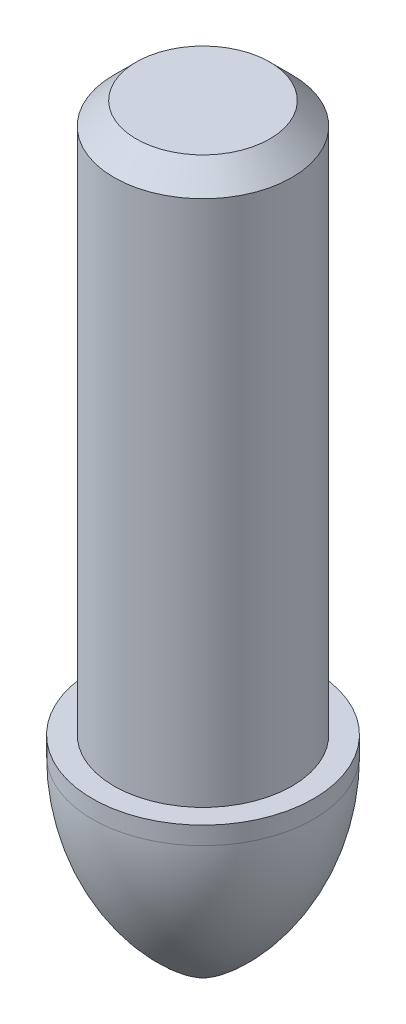
SolidWorks part; units mm, degrees
material "K110"
ref_plane "Front Plane" through (0, 0, 0) normal (0, 0, 1) x (1, 0, 0)
ref_plane "Top Plane" through (0, 0, 0) normal (0, 1, 0) x (1, 0, 0)
ref_plane "Right Plane" through (0, 0, 0) normal (1, 0, 0) x (0, 0, -1)
sketch "Sketch1" plane through (0, 0, 0) normal (0, 0, 1) x (1, 0, 0)
  line L0 (0, 0) -> (0, -39.1187) construction
  line L1 (0, 0) -> (4, 0)
  line L2 (4, 0) -> (4, -24.7)
  line L3 (4, -24.7) -> (4.976, -24.7)
  line L4 (4.976, -24.7) -> (4.976, -25.5)
  line L5 (4.976, -25.5) -> (-4.976, -25.5) construction
  line L6 (0, -33.8889) -> (0, 0)
  arc A1 (0.7148, -33.6644) -> (4.976, -25.5) centre (-4.976, -25.5) ccw
  arc A2 (0, -33.8889) -> (0.7148, -33.6644) centre (0, -32.6389) ccw
  arc A3 (0, -31.3889) -> (0, -33.8889) centre (0, -32.6389) ccw construction
  arc A4 (0.7148, -33.6644) -> (0, -31.3889) centre (0, -32.6389) ccw construction
  arc A5 (0, -34.1187) -> (0.7148, -33.6644) centre (-4.976, -25.5) ccw construction
  dimension "D6" = 2.5
  dimension "D1" = 9.952
  dimension "PilotDiameter" = 9.952
  dimension "D2" = 8
  dimension "D4" = 9.952
  dimension "ShankLength" = 25.5
  dimension "D3" = 0.8
  dimension "D5" = 5
revolve "Revolve1" add sketch "Sketch1" angle 360 about L0
chamfer "Chamfer1" distance 1 angle 45 1 edges at (-4, 0, 0)
cosmetic thread "Cosmetic Thread2" parameters "D1"=16, "D2"=6.619
equation "\"D4@Sketch1\" = \"PilotDiameter@Sketch1\""
equation "\"Pierce Punch Diameter\"= 10"
equation "\"PilotDiameter@Sketch1\"= \"Pierce Punch Diameter\" - 0.03 * 1.6"
equation "\"Material Thickness\" = 3mm"
equation "\"Punch Height\"= 20mm"
equation "\"ShankLength@Sketch1\"= \"Punch Height\" + \"Thread into Punch Holder\" + \"Pilot Engagement Length\" - 6"
equation "\"Thread into Punch Holder\"= 10mm"
equation "\"Pilot Engagement Length\"= \"Material Thickness\" * 0.5"
